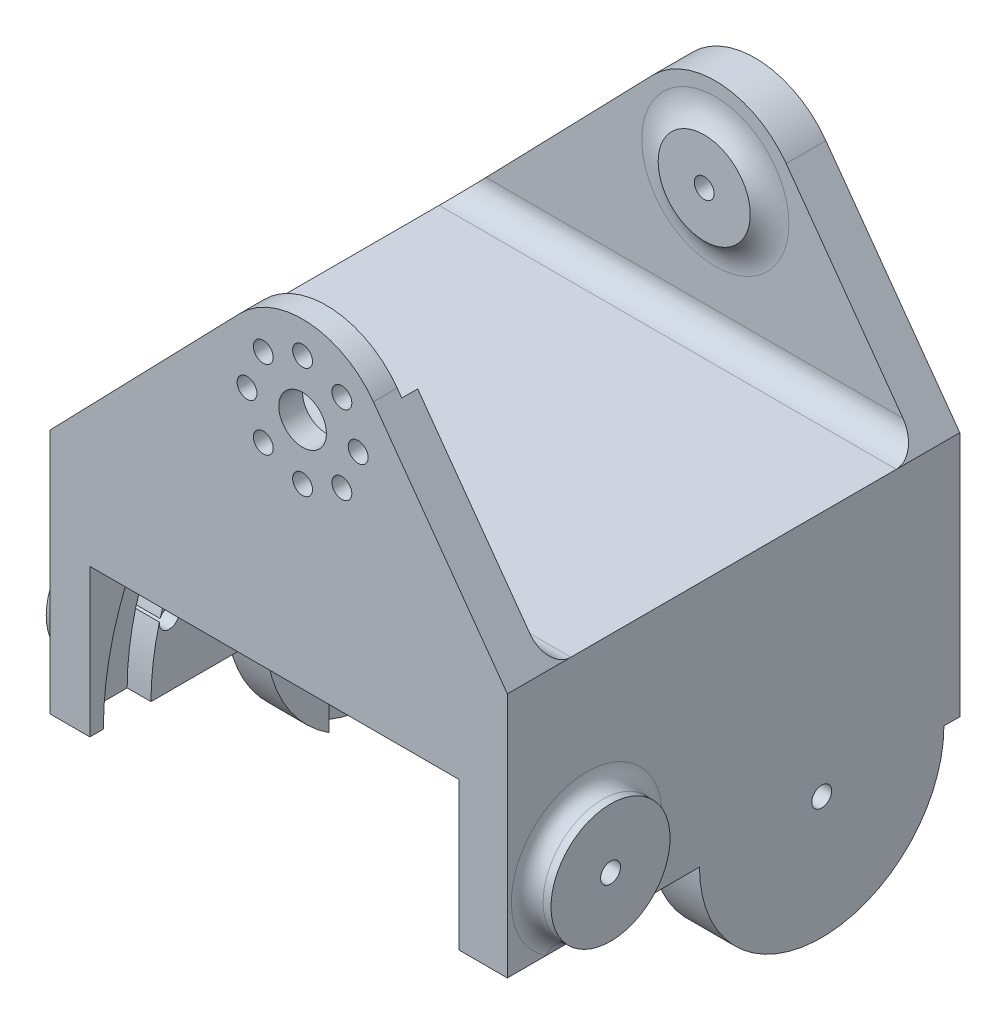
SolidWorks part; units mm, degrees
material "自訂玻璃纖維"
ref_plane "前基準面" through (0, 0, 0) normal (0, 0, 1) x (1, 0, 0)
ref_plane "上基準面" through (0, 0, 0) normal (0, 1, 0) x (1, 0, 0)
ref_plane "右基準面" through (0, 0, 0) normal (1, 0, 0) x (0, 0, -1)
sketch "草圖1" plane through (0, 0, 0) normal (0, 0, 1) x (1, 0, 0)
  line L0 (25.8, -18) -> (25.8, -17)
  line L1 (-31.8, -17) -> (-7.8981, 7.6564)
  line L2 (25.8, -17) -> (8.9259, 6.4287)
  line L3 (-31.8, -31) -> (-31.8, -35)
  line L4 (-31.8, -18) -> (-31.8, -31)
  line L5 (-25.8, -29.383) -> (18.7, -29.383)
  line L6 (18.7, -29.383) -> (18.7, -40.383)
  line L7 (25.8, -31) -> (25.8, -35)
  line L9 (-25.8, -29.383) -> (-25.8, -43)
  line L10 (25.8, -18) -> (25.8, -31)
  line L12 (-31.8, -45.617) -> (-31.8, -48)
  line L13 (-31.8, -38.617) -> (-31.8, -42)
  line L17 (25.8, -42) -> (25.8, -36)
  line L18 (-31.8, -17) -> (-31.8, -18)
  line L19 (-31.8, -48) -> (-25.8, -48)
  line L21 (25.8, -42) -> (25.8, -43)
  line L23 (-25.8, -43) -> (-25.8, -48)
  line L25 (18.7, -40.383) -> (18.7, -48)
  line L27 (18.7, -48) -> (25.8, -48)
  line L29 (-31.8, -45.617) -> (-31.8, -42)
  line L30 (25.8, -43) -> (25.8, -48)
  line L33 (-31.8, -35) -> (-31.8, -38.617)
  line L37 (25.8, -35) -> (25.8, -36)
  circle A0 centre (0, 0) radius 3
  circle A1 centre (0, 7) radius 1.25
  circle A2 centre (4.9497, 4.9497) radius 1.25
  circle A3 centre (7, 0) radius 1.25
  circle A4 centre (4.9497, -4.9497) radius 1.25
  circle A5 centre (0, -7) radius 1.25
  circle A6 centre (-4.9497, -4.9497) radius 1.25
  circle A7 centre (-7, 0) radius 1.25
  circle A8 centre (-4.9497, 4.9497) radius 1.25
  arc A9 (8.9259, 6.4287) -> (-7.8981, 7.6564) centre (0, 0) ccw
  point P21 (0, 0)
  point P46 (25.8, -37)
  point P49 (25.8, -17)
  point P52 (-31.8, -17)
  point P55 (-31.8, -37)
  point P58 (-25.8, -37)
  point P77 (-31.8, -45.617)
  dimension "D1" = 6
  dimension "D2" = 2.5
  dimension "D3" = 7
  dimension "D5" = 22
  dimension "D6" = 5
  dimension "D7" = 57.6
  dimension "D8" = 25.8
  dimension "D9" = 31
  dimension "D10" = 31
  dimension "D4" = 8
extrude "填料-伸長1" add sketch "草圖1" along normal blind 57
sketch "草圖2" plane through (-31.8, 0, 0) normal (-1, 0, 0) x (0, 0, 1)
  line L0 (57, -17) -> (57, -48) construction
  line L2 (0, -17) -> (0, -48) construction
  circle A1 centre (17.4, -48) radius 17.4
  dimension "D1" = 39.6
extrude "填料-伸長2" add sketch "草圖2" against normal up to surface (6 mm away) up to face at (-25.8, -38.6915, 28.5)
sketch "草圖3" plane through (-31.8, 0, 0) normal (-1, 0, 0) x (0, 0, 1)
  circle A0 centre (17.4, -48) radius 3
  circle A1 centre (17.4, -55) radius 1.25
  circle A2 centre (12.4503, -52.9497) radius 1.25
  circle A3 centre (10.4, -48) radius 1.25
  circle A4 centre (12.4503, -43.0503) radius 1.25
  circle A5 centre (17.4, -41) radius 1.25
  circle A6 centre (22.3497, -43.0503) radius 1.25
  circle A7 centre (24.4, -48) radius 1.25
  circle A8 centre (22.3497, -52.9497) radius 1.25
  point P21 (17.4, -48)
  dimension "D1" = 2.5
  dimension "D3" = 8
  dimension "D2" = 7
extrude "除料-伸長1" cut sketch "草圖3" against normal up to surface (6 mm away) up to face at (-25.8, -44.0332, 29.76)
ref_plane "平面1" through (0, -17, 0) normal (0, 1, 0) x (1, 0, 0)
sketch "草圖4" plane through (0, -17, 0) normal (0, 1, 0) x (1, 0, 0)
  line L0 (-31.8, -57) -> (-31.8, 0) construction
  line L1 (-31.8, -5) -> (25.8, -5)
  line L2 (-31.8, -5) -> (-31.8, -52)
  line L3 (-31.8, -52) -> (25.8, -52)
  line L4 (25.8, -5) -> (25.8, -52)
  line L5 (25.8, -57) -> (25.8, 0) construction
  line L6 (-7.8981, 0) -> (-31.8, 0) construction
  line L7 (-7.8981, -57) -> (-31.8, -57) construction
  dimension "D1" = 5
  dimension "D2" = 5
extrude "除料-伸長2" cut sketch "草圖4" along normal blind 30
sketch "草圖5" plane through (0, 0, 0) normal (0, 0, -1) x (-1, 0, 0)
  circle A0 centre (0, 0) radius 8.25
extrude "填料-伸長3" add sketch "草圖5" against normal up to surface (5 mm away) up to face at (-3.6997, 4.9497, 5)
sketch "草圖7" plane through (0, 0, 5) normal (0, 0, 1) x (1, 0, 0)
  circle A0 centre (0, 0) radius 5
  dimension "D1" = 10
extrude "填料-伸長4" add sketch "草圖7" along normal blind 2.4
sketch "草圖8" plane through (0, 0, 7.4) normal (0, 0, 1) x (1, 0, 0)
  circle A0 centre (0, 0) radius 1.25
  dimension "D1" = 2.5
extrude "除料-伸長3" cut sketch "草圖8" against normal up to surface (7.4 mm away) up to face at (-2.4886, -26.6753, 0)
sketch "草圖9" plane through (-31.8, 0, 0) normal (-1, 0, 0) x (0, 0, 1)
  circle A0 centre (47, -40) radius 1.25
  circle A1 centre (17.4, -48) radius 3 construction
  dimension "D1" = 8
  dimension "D2" = 29.6
  dimension "D3" = 2.5
extrude "除料-伸長4" cut sketch "草圖9" against normal mid plane 153
sketch "草圖10" plane through (25.8, 0, 0) normal (1, 0, 0) x (0, 0, -1)
  circle A0 centre (-17.4, -48) radius 15.4
extrude "填料-伸長5" add sketch "草圖10" against normal up to surface (7.1 mm away) up to face at (18.7, -40, 45.75)
sketch "草圖12" plane through (-25.8, 0, 0) normal (1, 0, 0) x (0, 0, -1)
  line L2 (-26.9, -48) -> (-26.9, -69.5312)
  line L3 (-26.9, -69.5312) -> (-7.9, -69.5312)
  line L4 (-7.9, -48) -> (-7.9, -69.5312)
  arc A0 (-7.9, -48) -> (-26.9, -48) centre (-17.4, -48) ccw
  dimension "D1" = 19
extrude "除料-伸長6" cut sketch "草圖12" against normal blind 4
sketch "草圖13" plane through (18.7, 0, 0) normal (-1, 0, 0) x (0, 0, 1)
  line L0 (57, -29.383) -> (57, -48) construction
  circle A0 centre (17.4, -48) radius 5
  dimension "D1" = 10
  dimension "D2" = 39.6
extrude "填料-伸長7" add sketch "草圖13" along normal blind 0.9
sketch "草圖11" plane through (25.8, 0, 0) normal (1, 0, 0) x (0, 0, -1)
  circle A0 centre (-17.4, -48) radius 1.25
  dimension "D1" = 2.5
extrude "除料-伸長7" cut sketch "草圖11" against normal up to surface (8 mm away) up to face at (17.8, -48, 22.4)
fillet "圓角4" radius 5 1 edges at (18.7, -48, 12.4)
fillet "圓角5" radius 5 1 edges at (5, 0, 5)
fillet "圓角6" radius 3 2 edges at (-3, -17, 52) (-3, -17, 5)
sketch "草圖14" plane through (0, 0, 52) normal (0, 0, -1) x (-1, 0, 0)
  line L0 (-9.5, 0) -> (-9.5, 12.7288)
  line L1 (-9.5, 12.7288) -> (9.5, 12.7288)
  line L2 (9.5, 12.7288) -> (9.5, 0)
  arc A0 (-9.5, 0) -> (9.5, 0) centre (0, 0) ccw
  dimension "D1" = 19
extrude "除料-伸長8" cut sketch "草圖14" against normal blind 2
sketch "草圖15" plane through (-25.8, 0, 0) normal (1, 0, 0) x (0, 0, -1)
  line L0 (-50.4124, -29.383) -> (-43.304, -29.383)
  line L1 (8.504, -29.383) -> (15.6124, -29.383)
  line L2 (-57, -29.383) -> (0, -29.383) construction
  arc A1 (-50.4124, -29.383) -> (15.6124, -29.383) centre (-17.4, -48) ccw
  arc A2 (-43.304, -29.383) -> (8.504, -29.383) centre (-17.4, -48) ccw
  dimension "D1" = 31.9
  dimension "D2" = 37.9
extrude "除料-伸長9" cut sketch "草圖15" against normal blind 4
sketch "草圖17" plane through (25.8, 0, 0) normal (1, 0, 0) x (0, 0, -1)
  circle A0 centre (-47, -40) radius 7.5
  dimension "D1" = 15
extrude "填料-伸長8" add sketch "草圖17" along normal blind 3
fillet "圓角7" radius 2 1 edges at (25.8, -40, 54.5)
sketch "草圖18" plane through (-31.8, 0, 0) normal (-1, 0, 0) x (0, 0, 1)
  circle A0 centre (47, -40) radius 7.5
  dimension "D1" = 15
extrude "填料-伸長9" add sketch "草圖18" along normal blind 3
fillet "圓角8" radius 2 1 edges at (-31.8, -40, 39.5)
sketch "草圖19" plane through (28.8, 0, 0) normal (1, 0, 0) x (0, 0, -1)
  circle A0 centre (-47, -40) radius 1.25
  dimension "D1" = 2.5
extrude "除料-伸長10" cut sketch "草圖19" against normal through all
sketch "草圖20" plane through (18.7, 0, 0) normal (-1, 0, 0) x (0, 0, 1)
  line L0 (-15.6124, -29.383) -> (-8.504, -29.383)
  line L1 (43.304, -29.383) -> (50.4124, -29.383)
  circle A0 centre (17.4, -48) radius 1.25 construction
  arc A1 (-15.6124, -29.383) -> (50.4124, -29.383) centre (17.4, -48) ccw
  arc A2 (-8.504, -29.383) -> (43.304, -29.383) centre (17.4, -48) ccw
  dimension "D1" = 31.9
  dimension "D2" = 37.9
  dimension "D3" = 51.808
extrude "除料-伸長11" cut sketch "草圖20" against normal blind 4
sketch "草圖21" plane through (18.7, 0, 0) normal (-1, 0, 0) x (0, 0, 1)
  line L1 (0, -29.383) -> (57, -29.383)
  line L2 (0, -29.383) -> (0, -72.3512)
  line L3 (0, -72.3512) -> (57, -72.3512)
  line L4 (57, -29.383) -> (57, -72.3512)
  circle A1 centre (17.4, -48) radius 7.8618
extrude "除料-伸長13" cut sketch "草圖21" against normal blind 1
sketch "草圖22" plane through (-25.8, 0, 0) normal (1, 0, 0) x (0, 0, -1)
  line L1 (-57, -29.383) -> (0, -29.383)
  line L2 (-57, -29.383) -> (-57, -79.663)
  line L3 (-57, -79.663) -> (0, -79.663)
  line L4 (0, -29.383) -> (0, -79.663)
extrude "除料-伸長14" cut sketch "草圖22" against normal blind 1
sketch "草圖23" plane through (0, 0, 7.4) normal (0, 0, 1) x (1, 0, 0)
  circle A0 centre (0, 0) radius 8.0037
extrude "除料-伸長15" cut sketch "草圖23" against normal blind 1
